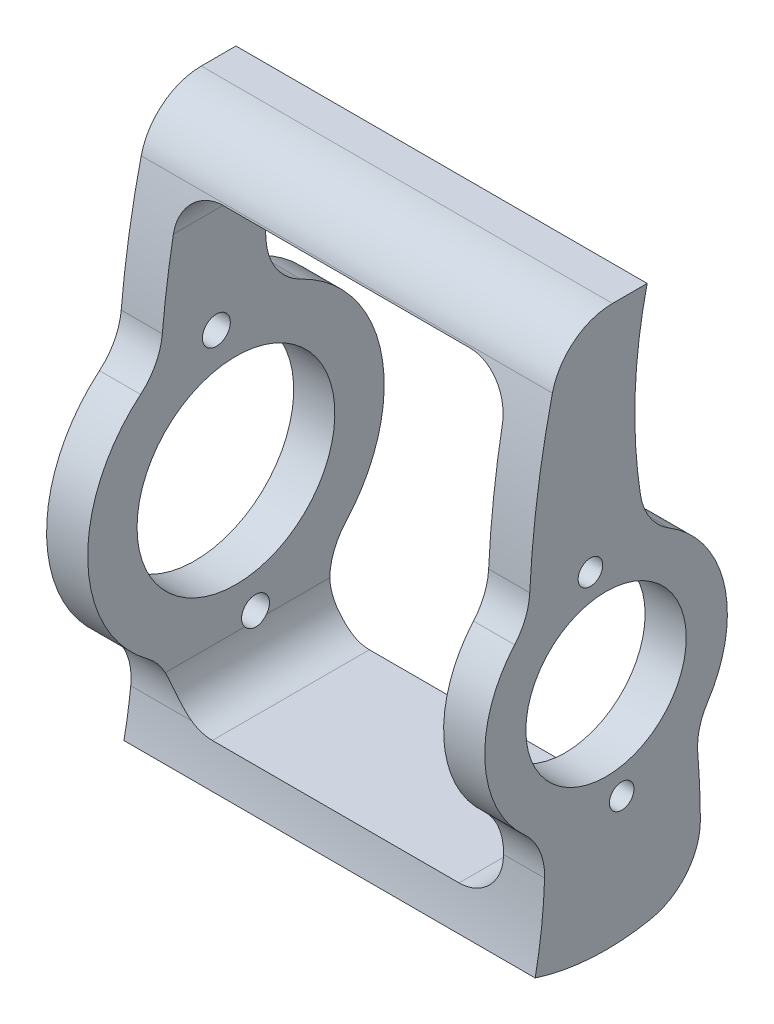
SolidWorks part; units mm, degrees
other "Markup2"
sketch "Sketch9" plane through (31.75, 50.4016, 20.35) normal (0.8402, 0.4575, 0.2911) x (0.3274, 0, -0.9449)
material "AISI 4340 Steel, normalized"
ref_plane "Front Plane" through (0, 0, 0) normal (0, 0, 1) x (1, 0, 0)
ref_plane "Top Plane" through (0, 0, 0) normal (0, 1, 0) x (1, 0, 0)
ref_plane "Right Plane" through (0, 0, 0) normal (1, 0, 0) x (0, 0, -1)
other "Center of Mass"
sketch "Weapon Layout" plane through (0, 0, 0) normal (1, 0, 0) x (0, 0, -1)
  line L0 (-6.35, 50.4016) -> (6.35, 50.4016) construction
  line L1 (-10.9443, -33.834) -> (14.4209, -32.5046) construction
  line L2 (6.35, 50.4016) -> (-5.4537, 0) construction
  line L3 (6.35, 50.4016) -> (0, 0) construction
  line L4 (0, 0) -> (0, -33.2604) construction
  circle A0 centre (0, 0) radius 14 construction
  circle A1 centre (0, 0) radius 50.8 construction
  circle A2 centre (0, 0) radius 17.175 construction
  circle A3 centre (0, 0) radius 20.35 construction
  arc A4 (-6.35, 50.4016) -> (-20.35, 0) centre (77.3756, 0) ccw construction
  arc A5 (23.3803, -26.7932) -> (-23.7089, -26.5029) centre (0, 0) cw construction
  arc A6 (6.35, 50.4016) -> (15.4347, 13.2625) centre (47.4536, 40.7754) ccw construction
  dimension "D1" = 28
  dimension "D2" = 101.6
  dimension "D3" = 3.175
  dimension "D4" = 6.35
  dimension "D5" = 12.7
  dimension "D7" = 6
  dimension "D6" = 15.24
  dimension "D8" = 25.4
  dimension "D9" = 87
sketch "Sketch2" plane through (0, 0, 0) normal (1, 0, 0) x (0, 0, -1)
  line L0 (-6.35, 50.4016) -> (6.35, 50.4016)
  line L1 (-11.3249, -1.5462) -> (0, 0) construction
  line L2 (6.35, 50.4016) -> (-5.4537, 0) construction
  line L3 (-11.5714, 0.7977) -> (-15.24, 50.4016) construction
  arc A0 (-10.9443, -33.834) -> (14.4209, -32.5046) centre (0, 0) ccw
  arc A1 (-23.7089, -26.5029) -> (23.3803, -26.7932) centre (0, 0) ccw construction
  arc A2 (-10.934, -3.8704) -> (-11.5714, 0.7977) centre (26.4248, 3.6078) cw
  arc A3 (9.7952, 6.5275) -> (11.7704, 0.1087) centre (-25.4904, -7.8439) cw
  arc A4 (-11.5714, 0.7977) -> (-6.35, 50.4016) centre (128.3504, 11.1461) cw
  arc A5 (-10.934, -3.8704) -> (-10.9443, -33.834) centre (-85.6518, -18.8267) cw
  arc A6 (6.35, 50.4016) -> (9.7952, 6.5275) centre (76.9323, 33.8717) ccw
  arc A7 (11.7704, 0.1087) -> (14.4209, -32.5046) centre (-112.4323, -26.3999) cw
  circle A9 centre (0, 0) radius 11.43 construction
  point P25 (10.9245, 3.3617)
  dimension "D1" = 127
  dimension "D2" = 38.1
  dimension "D3" = 76.2
  dimension "D4" = 38.1
  dimension "D5" = 22.86
  dimension "D6" = 8.89
extrude "Boss-Extrude2" add sketch "Sketch2" along normal mid plane 63.5
sketch "Sketch3" plane through (0, 0, 0) normal (0, 0, 1) x (1, 0, 0)
  line L0 (31.75, 50.4016) -> (-31.75, 50.4016) construction
  line L1 (-25.4, 42.7816) -> (25.4, 42.7816)
  line L2 (-25.4, 42.7816) -> (-25.4, -27.94)
  line L3 (-25.4, -27.94) -> (25.4, -27.94)
  line L4 (25.4, 42.7816) -> (25.4, -27.94)
  line L6 (-31.75, -35.56) -> (31.75, -35.56) construction
  line L7 (-31.75, 50.4016) -> (-31.75, 0.7977) construction
  dimension "D1" = 7.62
  dimension "D3" = 6.35
  dimension "D4" = 7.62
  dimension "D2" = 6.35
extrude "Cut-Extrude1" cut sketch "Sketch3" against normal through all both and the other way through all
fillet "Fillet1" radius 6.35 4 edges at (-25.4, 42.7816, 1.6753) (25.4, 42.7816, 1.6753) (25.4, -27.94, -2.2798) (-25.4, -27.94, -2.2798)
fillet "Fillet3" radius 9.525 2 edges at (0, -32.5046, -14.4209) (0, 50.4016, 6.35)
sketch "Sketch6" plane through (-31.75, 0, 0) normal (-1, 0, 0) x (0, 0, 1)
  circle A0 centre (0, 0) radius 22.89
  dimension "D1" = 45.78
extrude "Boss-Extrude3" add sketch "Sketch6" against normal up to surface (6.35 mm away) up to face at (-25.4, 4.1451, 0.3502)
sketch "Sketch7" plane through (-31.75, 0, 0) normal (-1, 0, 0) x (0, 0, 1)
  circle A0 centre (0, 0) radius 15.27
  arc A1 (9.4783, -20.8354) -> (11.6939, 19.6775) centre (0, 0) ccw construction
  dimension "D1" = 30.54
extrude "Cut-Extrude3" cut sketch "Sketch7" against normal up to next
sketch "Sketch10" plane through (31.75, 0, 0) normal (1, 0, 0) x (0, 0, -1)
  circle A0 centre (0, 0) radius 18.7325
  dimension "D1" = 37.465
extrude "Boss-Extrude4" add sketch "Sketch10" against normal up to surface (6.35 mm away) up to face at (25.4, 4.1451, 0.3502)
sketch "Sketch5" plane through (31.75, 0, 0) normal (1, 0, 0) x (0, 0, -1)
  circle A0 centre (0, 0) radius 12.3825
  circle A1 centre (0, 0) radius 6.35 construction
  dimension "D1" = 12.7
  dimension "D2" = 24.765
extrude "Cut-Extrude2" cut sketch "Sketch5" against normal up to next
fillet "Fillet2" radius 9.525 8 edges at (-28.575, 19.6775, 11.6939) (-28.575, -20.8354, 9.4783) (-28.575, -17.8878, -14.2821) (-28.575, 22.2493, -5.378) (28.575, 17.6489, -6.2788) (28.575, -12.645, -13.8207) (28.575, -16.1454, 9.499) (28.575, 14.4551, 11.9145)
sketch "Sketch11" plane through (31.75, 0, 0) normal (1, 0, 0) x (0, 0, -1)
  circle A0 centre (-2.4136, 16.1721) radius 1.8986
  circle A1 centre (-2.4136, 16.1721) radius 1.8986 construction
  circle A2 centre (2.4136, -16.1721) radius 1.8987
  circle A3 centre (2.4136, -16.1721) radius 1.8987 construction
extrude "Cut-Extrude4" cut sketch "Sketch11" against normal up to surface (6.35 mm away) up to face at (25.4, 12.3825, 0)
hole_wizard "#6 Clearance Hole1" positions "Sketch12" profile "Sketch13" hole size "#6" standard "ANSI Inch"
sketch "Sketch12" plane through (-31.75, 0, 0) normal (1, 0, 0) x (0, 0, -1)
  point P0 (-3.0235, 20.259)
  point P3 (3.0235, -20.259)
sketch "Sketch13" plane through (-31.75, 20.259, 3.0235) normal (0, 1, 0) x (0, 0, 1)
  line L0 (0, 0) -> (0, 8.9134)
  line L1 (0, 8.9134) -> (2.1526, 7.62)
  line L2 (2.1526, 7.62) -> (2.1526, 0)
  line L5 (2.1526, 0) -> (0, 0)
  line L10 (0, 8.9134) -> (-2.1527, 7.62) construction
  line L11 (0, -6.35) -> (0, 107.95) construction
  dimension "Hole Dia." = 4.3053
  dimension "Hole Depth" = 7.62
  dimension "Drill Angle" = 118
equation "\"D1@Weapon Layout\" = 28mm"
equation "\"D1@Sketch6\"=\"bearing OD L\"+1/2in+0.2in"
equation "\"D2@Sketch3\"=\"D3@Sketch3\""
equation "\"D1@Sketch7\"=\"bearing OD L\"+0.1in"
equation "\"D2@Sketch5\"=\"bearing OD R\" + .1"
equation "\"D1@Sketch10\"=\"bearing OD R\" + 1/2 + .1"
equation "\"bearing OD R\"= 7 / 8"
equation "\"bearing OD L\"= 28mm"
